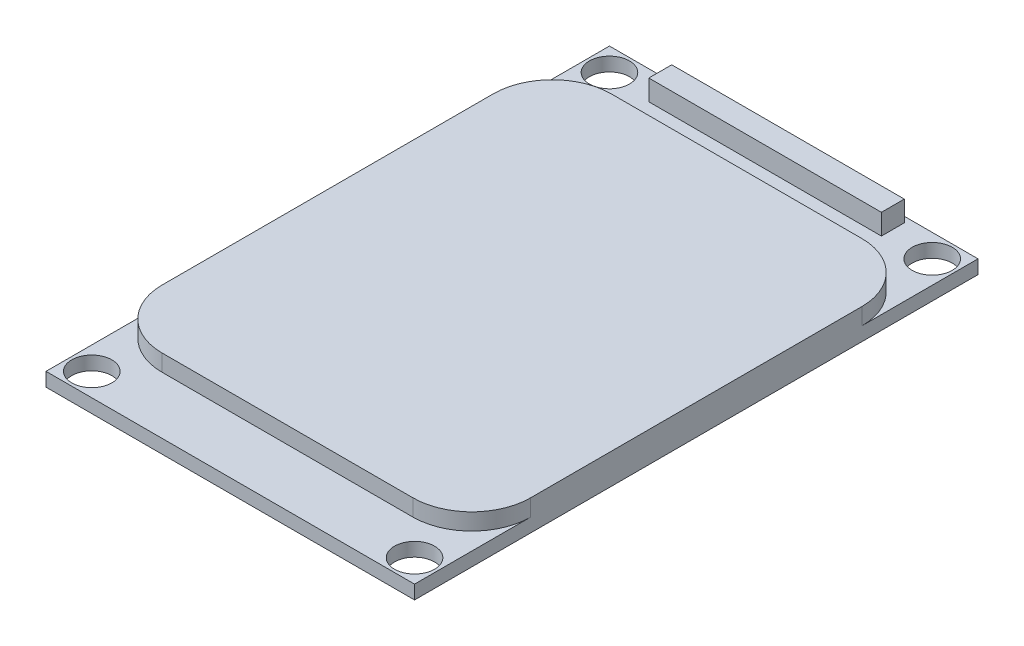
SolidWorks part; units mm, degrees
ref_plane "前视基准面" through (0, 0, 0) normal (0, 0, 1) x (1, 0, 0)
ref_plane "上视基准面" through (0, 0, 0) normal (0, 1, 0) x (1, 0, 0)
ref_plane "右视基准面" through (0, 0, 0) normal (1, 0, 0) x (0, 0, -1)
sketch "草图1" plane through (0, 0, 0) normal (0, 1, 0) x (1, 0, 0)
  line L1 (-15.1368, 18.3162) -> (17.0632, 18.3162)
  line L2 (-15.1368, 18.3162) -> (-15.1368, -30.9138)
  line L3 (-15.1368, -30.9138) -> (17.0632, -30.9138)
  line L4 (17.0632, 18.3162) -> (17.0632, -30.9138)
  dimension "D1" = 32.2
  dimension "D2" = 49.23
extrude "凸台-拉伸1" add sketch "草图1" along normal blind 1.2
sketch "草图2" plane through (0, 1.2, 0) normal (0, 1, 0) x (1, 0, 0)
  line L0 (17.0632, 18.3162) -> (-15.1368, 18.3162) construction
  line L1 (-13.1368, 16.3162) -> (15.0632, 16.3162) construction
  line L2 (-13.1368, 16.3162) -> (-13.1368, -28.9138) construction
  line L3 (-13.1368, -28.9138) -> (15.0632, -28.9138) construction
  line L4 (15.0632, 16.3162) -> (15.0632, -28.9138) construction
  line L5 (-15.1368, -30.9138) -> (17.0632, -30.9138) construction
  line L6 (-15.1368, 18.3162) -> (-15.1368, -30.9138) construction
  line L7 (17.0632, -30.9138) -> (17.0632, 18.3162) construction
  line L9 (-9.1968, 17.8162) -> (11.1232, 17.8162)
  line L10 (-9.1968, 17.8162) -> (-9.1968, 15.8162)
  line L11 (-9.1968, 15.8162) -> (11.1232, 15.8162)
  line L12 (11.1232, 17.8162) -> (11.1232, 15.8162)
  circle A0 centre (-13.1368, 16.3162) radius 1.75
  circle A1 centre (15.0632, 16.3162) radius 1.75
  circle A2 centre (-13.1368, -28.9138) radius 1.75
  circle A3 centre (15.0632, -28.9138) radius 1.75
  point P20 (-9.1968, 16.8162)
  point P21 (0.9632, 17.8162)
  point P22 (0.9632, 18.3162)
  dimension "D1" = 3.5
  dimension "D2" = 2
  dimension "D3" = 2
  dimension "D4" = 2
  dimension "D5" = 2
  dimension "D6" = 1.5
  dimension "D7" = 20.32
  dimension "D8" = 2.5
extrude "凸台-拉伸2" add sketch "草图2" along normal blind 1.8 contours L9 L12 L11 L10
extrude "切除-拉伸1" cut sketch "草图2<3>" against normal blind 1.8 contours A3 | A1 | A0 | A2 region at (-13.1368, 1.2, -16.3162) region at (15.0632, 1.2, -16.3162) region at (-13.1368, 1.2, 28.9138) region at (15.0632, 1.2, 28.9138)
sketch "草图2<3>" plane through (0, 1.2, 0) normal (0, 1, 0) x (1, 0, 0) same geometry as "草图2"
sketch "草图3" plane through (0, 1.2, 0) normal (0, 1, 0) x (1, 0, 0)
  line L0 (-9.9868, 13.3162) -> (11.9132, 13.3162)
  line L1 (-15.1368, 18.3162) -> (-15.1368, -30.9138) construction
  line L2 (17.0632, -30.9138) -> (17.0632, 18.3162) construction
  line L3 (17.0632, 8.1662) -> (17.0632, -20.7638)
  line L4 (11.9132, -25.9138) -> (-9.9868, -25.9138)
  line L5 (-15.1368, -20.7638) -> (-15.1368, 8.1662)
  line L6 (17.0632, 18.3162) -> (-15.1368, 18.3162) construction
  arc A2 (-9.9868, 13.3162) -> (-15.1368, 8.1662) centre (-9.9868, 8.1662) ccw
  arc A3 (-15.1368, -20.7638) -> (-9.9868, -25.9138) centre (-9.9868, -20.7638) ccw
  arc A4 (17.0632, -20.7638) -> (11.9132, -25.9138) centre (11.9132, -20.7638) cw
  arc A5 (17.0632, 8.1662) -> (11.9132, 13.3162) centre (11.9132, 8.1662) ccw
  point P12 (-15.1368, -25.9138)
  point P15 (17.0632, -25.9138)
  point P18 (-15.1368, 13.3162)
  point P21 (17.0632, 13.3162)
  dimension "D3" = 5.15
  dimension "D1" = 39.23
  dimension "D2" = 5
extrude "凸台-拉伸3" add sketch "草图3" along normal blind 1.46
sketch "草图4" plane through (0, 1.2, 0) normal (0, 1, 0) x (1, 0, 0)
  line L4 (11.9132, -25.9138) -> (-9.9868, -25.9138)
  line L5 (-15.1368, -20.7638) -> (-15.1368, -30.9138)
  line L6 (-15.1368, -30.9138) -> (17.0632, -30.9138)
  line L7 (17.0632, -30.9138) -> (17.0632, -20.7638)
  line L8 (11.9132, -25.9138) -> (-9.9868, -25.9138)
  line L9 (-15.1368, -20.7638) -> (-15.1368, -30.9138)
  line L10 (-15.1368, -30.9138) -> (17.0632, -30.9138)
  line L11 (17.0632, -30.9138) -> (17.0632, -20.7638)
  line L12 (-9.9868, 13.3162) -> (11.9132, 13.3162)
  line L13 (17.0632, 8.1662) -> (17.0632, 18.3162)
  line L14 (17.0632, 18.3162) -> (-15.1368, 18.3162)
  line L15 (-15.1368, 18.3162) -> (-15.1368, 8.1662)
  line L16 (-9.9868, 13.3162) -> (11.9132, 13.3162)
  line L17 (17.0632, 8.1662) -> (17.0632, 18.3162)
  line L18 (17.0632, 18.3162) -> (-15.1368, 18.3162)
  line L19 (-15.1368, 18.3162) -> (-15.1368, 8.1662)
  arc A2 (-15.1368, -20.7638) -> (-9.9868, -25.9138) centre (-9.9868, -20.7638) ccw
  arc A3 (11.9132, -25.9138) -> (17.0632, -20.7638) centre (11.9132, -20.7638) ccw
  arc A4 (-15.1368, -20.7638) -> (-9.9868, -25.9138) centre (-9.9868, -20.7638) ccw
  arc A5 (11.9132, -25.9138) -> (17.0632, -20.7638) centre (11.9132, -20.7638) ccw
  arc A6 (17.0632, 8.1662) -> (11.9132, 13.3162) centre (11.9132, 8.1662) ccw
  arc A7 (-9.9868, 13.3162) -> (-15.1368, 8.1662) centre (-9.9868, 8.1662) ccw
  arc A8 (17.0632, 8.1662) -> (11.9132, 13.3162) centre (11.9132, 8.1662) ccw
  arc A9 (-9.9868, 13.3162) -> (-15.1368, 8.1662) centre (-9.9868, 8.1662) ccw
  dimension "D1" = 0
  dimension "D2" = 0
